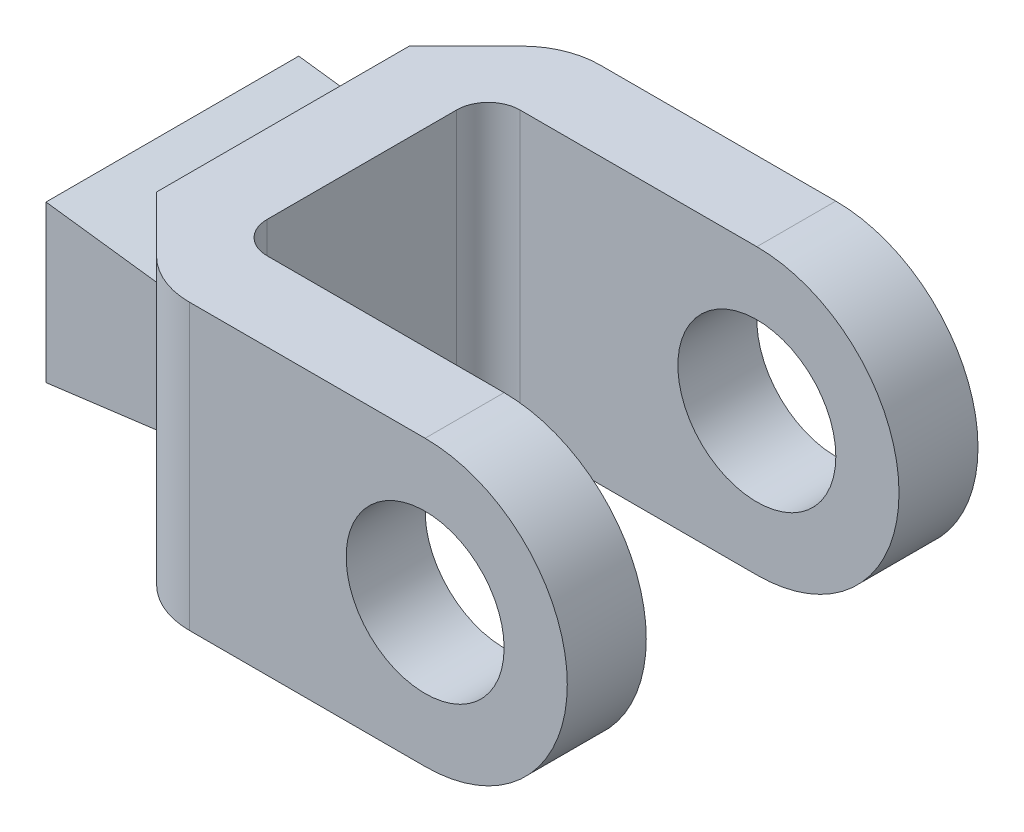
SolidWorks part; units mm, degrees
ref_plane "Front Plane" through (0, 0, 0) normal (0, 0, 1) x (1, 0, 0)
ref_plane "Top Plane" through (0, 0, 0) normal (0, 1, 0) x (1, 0, 0)
ref_plane "Right Plane" through (0, 0, 0) normal (1, 0, 0) x (0, 0, -1)
sketch "Sketch1" plane through (0, 0, 0) normal (0, 0, 1) x (1, 0, 0)
  line L0 (-2.2687, 0) -> (4.5375, 0) construction
  line L4 (-1.75, -2.475) -> (-1.75, 2.475)
  line L5 (1.4583, -2.0625) -> (-1.75, 2.475) construction
  line L6 (1.4583, 2.0625) -> (-1.75, -2.475) construction
  line L7 (-1.75, -2.475) -> (1.75, -2.025)
  line L8 (-1.75, 2.475) -> (1.75, 2.025)
  line L21 (1.75, 2.025) -> (1.75, 4.5)
  line L22 (4.25, -4.5) -> (1.75, -4.5)
  line L25 (4.25, -4.5) -> (4.25, 4.5)
  line L26 (4.25, 4.5) -> (1.75, 4.5)
  line L27 (1.75, -4.5) -> (1.75, -2.025)
  line L28 (4.25, -4.5) -> (1.75, 4.5) construction
  line L29 (4.25, 4.5) -> (1.75, -4.5) construction
  point P0 (0, 0)
  point P2 (3, 0)
  point P3 (3, 0)
  point P6 (1.75, 2.025)
  point P9 (1.75, -2.025)
  dimension "D1" = 4.95
  dimension "D2" = 2.5
  dimension "D3" = 9
extrude "Boss-Extrude1" add sketch "Sketch1" along normal blind 8 contours L8 L21 L26 L25 L22 L27 L7 L4
sketch "Sketch2" plane through (0, 0, 0) normal (0, 0, 1) x (1, 0, 0)
  line L0 (-1.75, 0) -> (25.7432, 0) construction
  line L1 (-1.75, -2.475) -> (-1.75, 2.475) construction
  line L3 (12.75, -4.5) -> (1.75, -4.5)
  line L5 (12.75, 4.5) -> (1.75, 4.5)
  line L6 (1.75, -4.5) -> (1.75, 4.5)
  line L7 (15.7356, -3.3669) -> (1.75, 4.5) construction
  line L8 (15.7356, 3.3669) -> (1.75, -4.5) construction
  line L11 (1.75, -4.5) -> (1.75, -2.025) construction
  arc A0 (12.75, -4.5) -> (12.75, 4.5) centre (12.75, 0) ccw
  circle A1 centre (12.75, 0) radius 2.5
  circle A2 centre (12.75, 0) radius 7.5 construction
  point P5 (9.75, 0)
  point P7 (17.25, 0)
  dimension "D3" = 5
  dimension "D4" = 15
  dimension "D1" = 15.5
  dimension "D2" = 9
extrude "Boss-Extrude3" add sketch "Sketch2" against normal blind 2.5
sketch "Sketch5" plane through (0, 0, 0) normal (0, 1, 0) x (1, 0, 0)
  line L0 (4.25, 0) -> (4.25, 4.091) construction
  line L1 (12.75, 2.5) -> (1.75, 2.5) construction
  line L2 (1.75, 0) -> (4.25, 2.5)
  line L3 (4.25, 2.5) -> (1.75, 2.5)
  line L4 (1.75, 2.5) -> (1.75, 0)
  point P3 (4.25, 2.5)
extrude "Cut-Extrude2" cut sketch "Sketch5" against normal through all and the other way through all
fillet "Fillet5" radius 1 1 edges at (4.25, 0, 0)
fillet "Fillet6" radius 2.5 1 edges at (4.25, 0, -2.5)
ref_plane "Plane1" through (0, 0, 4) normal (0, 0, -1) x (-1, 0, 0)
mirror "Mirror2" about plane through (0, 0, 4) normal (0, 0, -1) of "Cut-Extrude2", "Fillet6", "Fillet5", "Boss-Extrude3"
